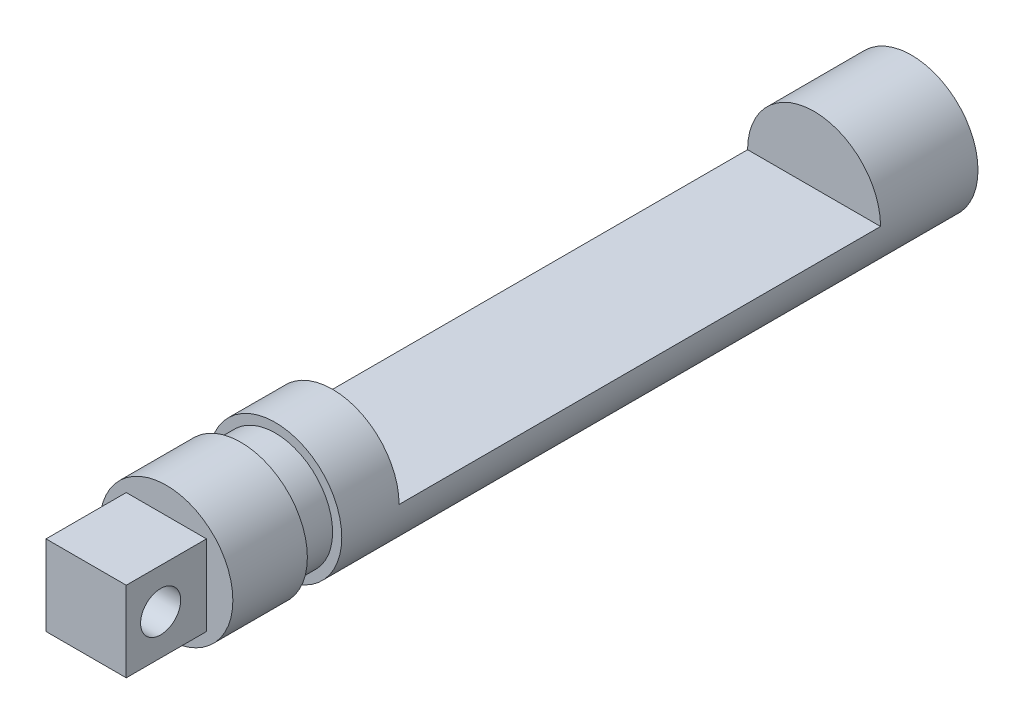
SolidWorks part; units mm, degrees
ref_plane "Alzado" through (0, 0, 0) normal (0, 0, 1) x (1, 0, 0)
ref_plane "Planta" through (0, 0, 0) normal (0, 1, 0) x (1, 0, 0)
ref_plane "Vista lateral" through (0, 0, 0) normal (1, 0, 0) x (0, 0, -1)
sketch "Croquis1" plane through (0, 0, 0) normal (0, 0, 1) x (1, 0, 0)
  circle A0 centre (0, 0) radius 5.8
  dimension "D1" = 11.6
extrude "Saliente-Extruir1" add sketch "Croquis1" along normal mid plane 65
sketch "Croquis2" plane through (0, 0, 0) normal (0, 0, 1) x (1, 0, 0)
  line L0 (-5.8, 0) -> (5.8, 0)
  circle A0 centre (0, 0) radius 5.8 construction
  arc A1 (5.8, 0) -> (-5.8, 0) centre (0, 0) ccw
extrude "Cortar-Extruir1" cut sketch "Croquis2" against normal blind 24
sketch "Croquis3" plane through (0, 0, 32.5) normal (0, 0, 1) x (1, 0, 0)
  circle A0 centre (0, 0) radius 5
  dimension "D1" = 10
extrude "Cortar-Extruir-Lámina1" cut sketch "Croquis3" against normal blind 3 from offset 6.5 thin offset against normal yes thin type one direction wall 0.8
sketch "Croquis4" plane through (0, 0, 32.5) normal (0, 0, 1) x (1, 0, 0)
  line L1 (-3.5, 3.5) -> (3.5, 3.5)
  line L2 (-3.5, 3.5) -> (-3.5, -3.5)
  line L3 (-3.5, -3.5) -> (3.5, -3.5)
  line L4 (3.5, 3.5) -> (3.5, -3.5)
  line L5 (-3.5, 3.5) -> (3.5, -3.5) construction
  line L6 (-3.5, -3.5) -> (3.5, 3.5) construction
  point P0 (0, 0)
  dimension "D1" = 7
  dimension "D2" = 7
extrude "Saliente-Extruir2" add sketch "Croquis4" along normal blind 7
sketch "Croquis6" plane through (-3.5, 0, 0) normal (-1, 0, 0) x (0, 0, 1)
  line L1 (0, 0) -> (36.5, 0) construction
  line L2 (32.5, 3.5) -> (32.5, -3.5) construction
  circle A0 centre (36.5, 0) radius 1.75
  dimension "D1" = 3.5
  dimension "D2" = 4
extrude "Cortar-Extruir3" cut sketch "Croquis6" against normal through all
extrude "Cortar-Extruir4" cut sketch "Croquis2<2>" along normal blind 18
sketch "Croquis2<2>" plane through (0, 0, 0) normal (0, 0, 1) x (1, 0, 0) same geometry as "Croquis2"
